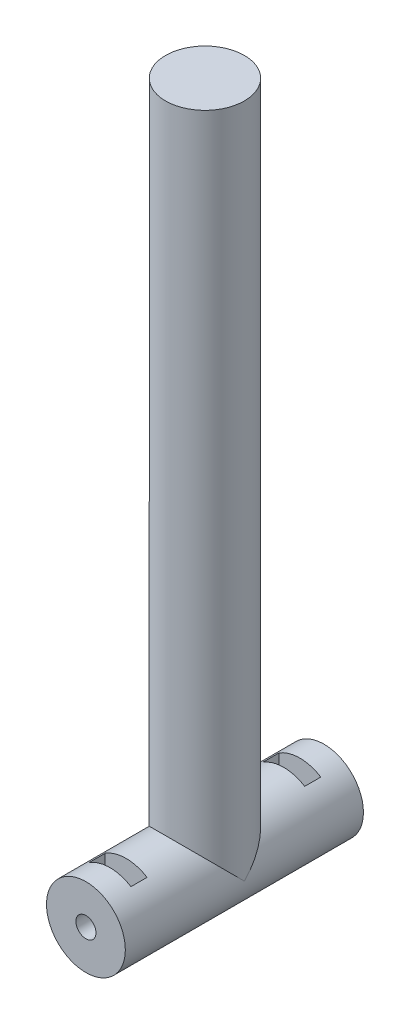
SolidWorks part; units mm, degrees
ref_plane "Front Plane" through (0, 0, 0) normal (0, 0, 1) x (1, 0, 0)
ref_plane "Top Plane" through (0, 0, 0) normal (0, 1, 0) x (1, 0, 0)
ref_plane "Right Plane" through (0, 0, 0) normal (1, 0, 0) x (0, 0, -1)
sketch "Sketch1" plane through (0, 0, 0) normal (0, 0, 1) x (1, 0, 0)
  circle A0 centre (0, 0) radius 4.9
extrude "Boss-Extrude1" add sketch "Sketch1" along normal blind 14.8 and the other way blind 14.8
sketch "Sketch2" plane through (0, 0, 0) normal (0, 1, 0) x (1, 0, 0)
  circle A0 centre (0, 0) radius 4.9
extrude "Boss-Extrude2" add sketch "Sketch2" along normal blind 84
ref_plane "Plane1" through (0, 0, 11.8) normal (0, 0, 1) x (1, 0, 0)
sketch "Sketch4" plane through (0, 0, 11.8) normal (0, 0, 1) x (1, 0, 0)
  line L1 (2.5981, 0) -> (1.299, 2.25)
  line L2 (1.299, 2.25) -> (-1.299, 2.25)
  line L3 (-1.299, 2.25) -> (-2.5981, 0)
  line L4 (-2.5981, 0) -> (-1.299, -2.25)
  line L5 (-1.299, -2.25) -> (1.299, -2.25)
  line L6 (1.299, -2.25) -> (2.5981, 0)
  circle A0 centre (0, 0) radius 2.25 construction
extrude "Cut-Extrude1" cut sketch "Sketch4" against normal blind 2
sketch "Sketch5" plane through (0, 0, 0) normal (0, 1, 0) x (1, 0, 0)
  line L0 (-2.5981, -9.8) -> (-2.5981, -11.8)
  line L1 (-5.39, -11.8) -> (5.39, -11.8) construction
  line L2 (-2.5981, -11.8) -> (2.5981, -11.8)
  line L3 (2.5981, -11.8) -> (2.5981, -9.8)
  line L4 (2.5981, -9.8) -> (-2.5981, -9.8)
extrude "Cut-Extrude2" cut sketch "Sketch5" along normal blind 12
mirror "Mirror2" about plane through (0, 0, 0) normal (0, 0, 1) of "Cut-Extrude2", "Cut-Extrude1"
sketch "Sketch6" plane through (0, 0, -14.8) normal (0, 0, -1) x (-1, 0, 0)
  circle A0 centre (0, 0) radius 1.25
extrude "Cut-Extrude3" cut sketch "Sketch6" against normal blind 10
mirror "Mirror3" about plane through (0, 0, 0) normal (0, 0, 1) of "Cut-Extrude3"
